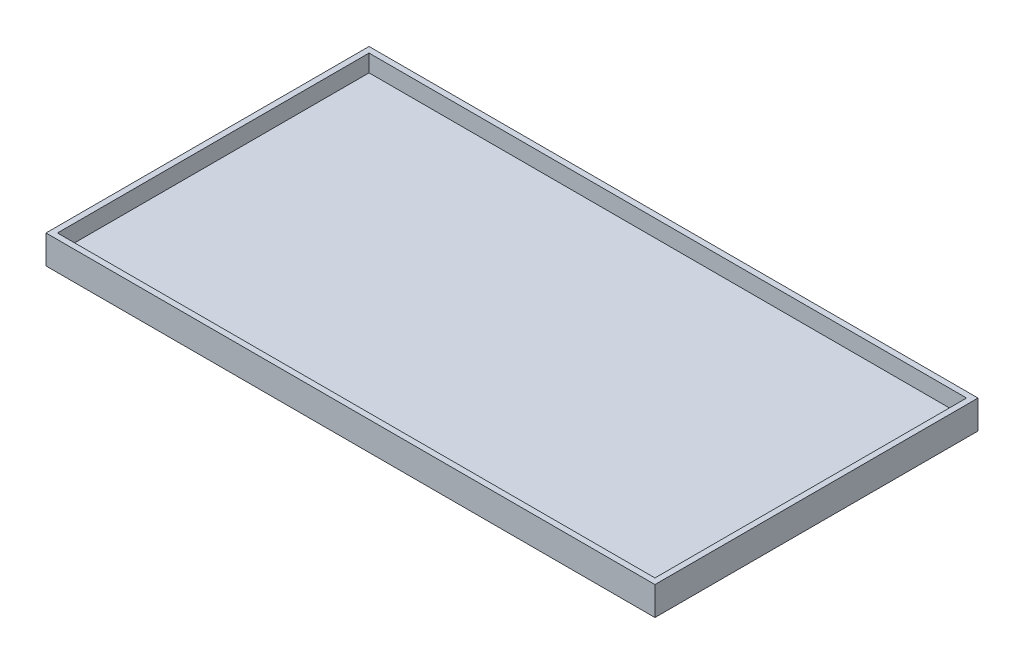
SolidWorks part; units mm, degrees
ref_plane "Front Plane" through (0, 0, 0) normal (0, 0, 1) x (1, 0, 0)
ref_plane "Top Plane" through (0, 0, 0) normal (0, 1, 0) x (1, 0, 0)
ref_plane "Right Plane" through (0, 0, 0) normal (1, 0, 0) x (0, 0, -1)
sketch "Sketch1" plane through (0, 0, 0) normal (0, 1, 0) x (1, 0, 0)
  line L1 (-53.25, 28.25) -> (53.25, 28.25)
  line L2 (-53.25, 28.25) -> (-53.25, -28.25)
  line L3 (-53.25, -28.25) -> (53.25, -28.25)
  line L4 (53.25, 28.25) -> (53.25, -28.25)
  line L5 (-53.25, 28.25) -> (53.25, -28.25) construction
  line L6 (-53.25, -28.25) -> (53.25, 28.25) construction
  line L7 (-52.25, 27.25) -> (52.25, 27.25)
  line L8 (-52.25, 27.25) -> (-52.25, -27.25)
  line L9 (-52.25, -27.25) -> (52.25, -27.25)
  line L10 (52.25, 27.25) -> (52.25, -27.25)
  line L11 (-52.25, 27.25) -> (52.25, -27.25) construction
  line L12 (-52.25, -27.25) -> (52.25, 27.25) construction
  point P0 (0, 0)
  point P6 (0, 0)
  dimension "D1" = 56.5
  dimension "D2" = 106.5
  dimension "D3" = 54.5
  dimension "D4" = 104.5
extrude "Boss-Extrude1" add sketch "Sketch1" along normal blind 5
sketch "Sketch2" plane through (0, 0, 0) normal (0, 1, 0) x (1, 0, 0)
  line L1 (-53.25, -28.25) -> (53.25, -28.25)
  line L2 (-53.25, -28.25) -> (-53.25, 28.25)
  line L3 (-53.25, 28.25) -> (53.25, 28.25)
  line L4 (53.25, -28.25) -> (53.25, 28.25)
  line L5 (-53.25, -28.25) -> (53.25, 28.25) construction
  line L6 (-53.25, 28.25) -> (53.25, -28.25) construction
  point P0 (0, 0)
  dimension "D1" = 106.5
  dimension "D2" = 56.5
extrude "Boss-Extrude2" add sketch "Sketch2" along normal blind 2
